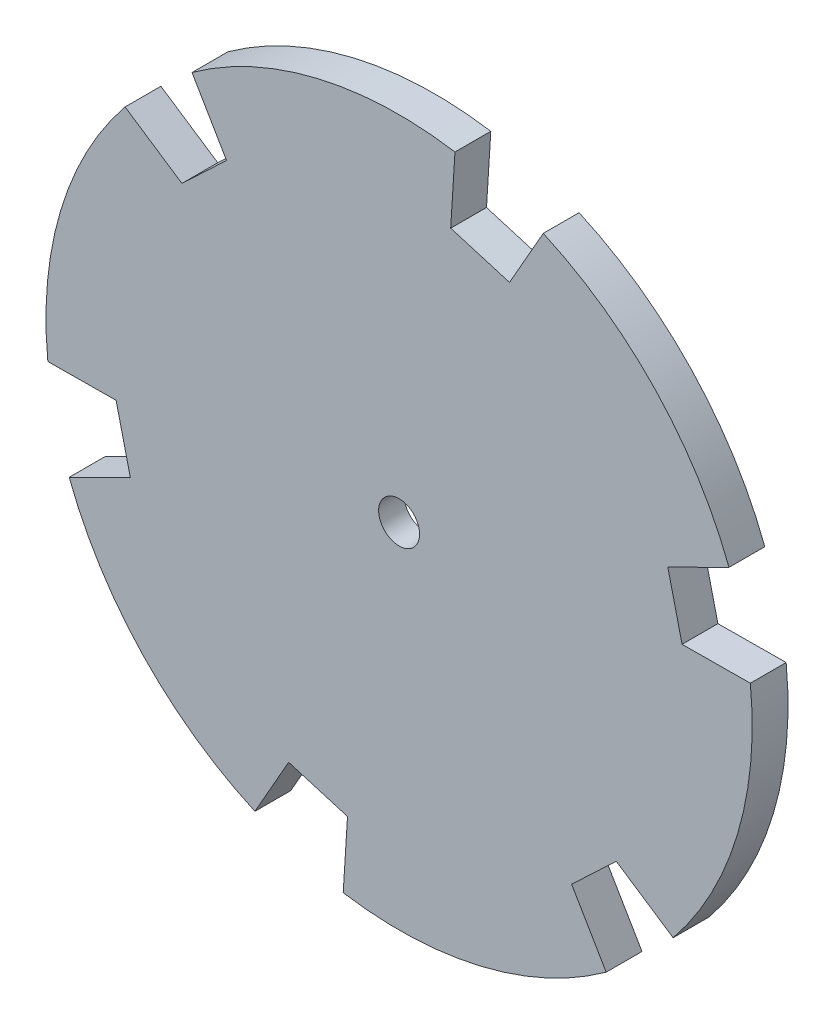
SolidWorks part; units mm, degrees
ref_plane "Front Plane" through (0, 0, 0) normal (0, 0, 1) x (1, 0, 0)
ref_plane "Top Plane" through (0, 0, 0) normal (0, 1, 0) x (1, 0, 0)
ref_plane "Right Plane" through (0, 0, 0) normal (1, 0, 0) x (0, 0, -1)
sketch "Sketch1" plane through (0, 0, 0) normal (0, 0, 1) x (1, 0, 0)
  line L18 (-20.2324, 27.9446) -> (-16.8562, 22.1912)
  line L19 (-16.8562, 22.1912) -> (-21.2157, 18.0687)
  line L20 (-21.2157, 18.0687) -> (-26.7716, 21.7608)
  line L21 (-34.3169, -3.5495) -> (-27.6463, -3.5023)
  line L22 (-27.6463, -3.5023) -> (-26.2558, -9.339)
  line L23 (-26.2558, -9.339) -> (-32.2312, -12.3045)
  line L24 (-14.0845, -31.4941) -> (-10.79, -25.6935)
  line L25 (-10.79, -25.6935) -> (-5.0401, -27.4076)
  line L26 (-5.0401, -27.4076) -> (-5.4596, -34.0653)
  line L27 (20.2324, -27.9446) -> (16.8562, -22.1912)
  line L28 (16.8562, -22.1912) -> (21.2157, -18.0687)
  line L29 (21.2157, -18.0687) -> (26.7716, -21.7608)
  line L30 (34.3169, 3.5495) -> (27.6463, 3.5023)
  line L31 (27.6463, 3.5023) -> (26.2558, 9.339)
  line L32 (26.2558, 9.339) -> (32.2312, 12.3045)
  line L33 (14.0845, 31.4941) -> (10.79, 25.6935)
  line L34 (10.79, 25.6935) -> (5.0401, 27.4076)
  line L35 (5.0401, 27.4076) -> (5.4596, 34.0653)
  line L36 (-20.2324, 27.9446) -> (-16.8562, 22.1912)
  line L37 (-16.8562, 22.1912) -> (-21.2157, 18.0687)
  line L38 (-21.2157, 18.0687) -> (-26.7716, 21.7608)
  line L39 (-34.3169, -3.5495) -> (-27.6463, -3.5023)
  line L40 (-27.6463, -3.5023) -> (-26.2558, -9.339)
  line L41 (-26.2558, -9.339) -> (-32.2312, -12.3045)
  line L42 (-14.0845, -31.4941) -> (-10.79, -25.6935)
  line L43 (-10.79, -25.6935) -> (-5.0401, -27.4076)
  line L44 (-5.0401, -27.4076) -> (-5.4596, -34.0653)
  line L45 (20.2324, -27.9446) -> (16.8562, -22.1912)
  line L46 (16.8562, -22.1912) -> (21.2157, -18.0687)
  line L47 (21.2157, -18.0687) -> (26.7716, -21.7608)
  line L48 (34.3169, 3.5495) -> (27.6463, 3.5023)
  line L49 (27.6463, 3.5023) -> (26.2558, 9.339)
  line L50 (26.2558, 9.339) -> (32.2312, 12.3045)
  line L51 (14.0845, 31.4941) -> (10.79, 25.6935)
  line L52 (10.79, 25.6935) -> (5.0401, 27.4076)
  line L53 (5.0401, 27.4076) -> (5.4596, 34.0653)
  arc A6 (-26.7716, 21.7608) -> (-34.3169, -3.5495) centre (0, 0) ccw
  arc A7 (-32.2312, -12.3045) -> (-14.0845, -31.4941) centre (0, 0) ccw
  arc A8 (-5.4596, -34.0653) -> (20.2324, -27.9446) centre (0, 0) ccw
  arc A9 (26.7716, -21.7608) -> (34.3169, 3.5495) centre (0, 0) ccw
  arc A10 (32.2312, 12.3045) -> (14.0845, 31.4941) centre (0, 0) ccw
  arc A11 (5.4596, 34.0653) -> (-20.2324, 27.9446) centre (0, 0) ccw
  arc A12 (-26.7716, 21.7608) -> (-34.3169, -3.5495) centre (0, 0) ccw
  arc A13 (-32.2312, -12.3045) -> (-14.0845, -31.4941) centre (0, 0) ccw
  arc A14 (-5.4596, -34.0653) -> (20.2324, -27.9446) centre (0, 0) ccw
  arc A15 (26.7716, -21.7608) -> (34.3169, 3.5495) centre (0, 0) ccw
  arc A16 (32.2312, 12.3045) -> (14.0845, 31.4941) centre (0, 0) ccw
  arc A17 (5.4596, 34.0653) -> (-20.2324, 27.9446) centre (0, 0) ccw
  dimension "D1" = 0
extrude "Boss-Extrude1" add sketch "Sketch1" along normal blind 2.5
sketch "Sketch2" plane through (0, 0, 0) normal (0, 0, -1) x (-1, 0, 0)
  line L18 (-5.4596, 34.0653) -> (-5.0401, 27.4076)
  line L19 (-5.0401, 27.4076) -> (-10.79, 25.6935)
  line L20 (-10.79, 25.6935) -> (-14.0845, 31.4941)
  line L21 (-32.2312, 12.3045) -> (-26.2558, 9.339)
  line L22 (-26.2558, 9.339) -> (-27.6463, 3.5023)
  line L23 (-27.6463, 3.5023) -> (-34.3169, 3.5495)
  line L24 (-26.7716, -21.7608) -> (-21.2157, -18.0687)
  line L25 (-21.2157, -18.0687) -> (-16.8562, -22.1912)
  line L26 (-16.8562, -22.1912) -> (-20.2324, -27.9446)
  line L27 (5.4596, -34.0653) -> (5.0401, -27.4076)
  line L28 (5.0401, -27.4076) -> (10.79, -25.6935)
  line L29 (10.79, -25.6935) -> (14.0845, -31.4941)
  line L30 (32.2312, -12.3045) -> (26.2558, -9.339)
  line L31 (26.2558, -9.339) -> (27.6463, -3.5023)
  line L32 (27.6463, -3.5023) -> (34.3169, -3.5495)
  line L33 (26.7716, 21.7608) -> (21.2157, 18.0687)
  line L34 (21.2157, 18.0687) -> (16.8562, 22.1912)
  line L35 (16.8562, 22.1912) -> (20.2324, 27.9446)
  line L36 (-5.4596, 34.0653) -> (-5.0401, 27.4076)
  line L37 (-5.0401, 27.4076) -> (-10.79, 25.6935)
  line L38 (-10.79, 25.6935) -> (-14.0845, 31.4941)
  line L39 (-32.2312, 12.3045) -> (-26.2558, 9.339)
  line L40 (-26.2558, 9.339) -> (-27.6463, 3.5023)
  line L41 (-27.6463, 3.5023) -> (-34.3169, 3.5495)
  line L42 (-26.7716, -21.7608) -> (-21.2157, -18.0687)
  line L43 (-21.2157, -18.0687) -> (-16.8562, -22.1912)
  line L44 (-16.8562, -22.1912) -> (-20.2324, -27.9446)
  line L45 (5.4596, -34.0653) -> (5.0401, -27.4076)
  line L46 (5.0401, -27.4076) -> (10.79, -25.6935)
  line L47 (10.79, -25.6935) -> (14.0845, -31.4941)
  line L48 (32.2312, -12.3045) -> (26.2558, -9.339)
  line L49 (26.2558, -9.339) -> (27.6463, -3.5023)
  line L50 (27.6463, -3.5023) -> (34.3169, -3.5495)
  line L51 (26.7716, 21.7608) -> (21.2157, 18.0687)
  line L52 (21.2157, 18.0687) -> (16.8562, 22.1912)
  line L53 (16.8562, 22.1912) -> (20.2324, 27.9446)
  circle A0 centre (0, 0) radius 3.875 construction
  circle A1 centre (0, 0) radius 3.875 construction
  circle A2 centre (0, 0) radius 4.075
  arc A6 (20.2324, 27.9446) -> (-5.4596, 34.0653) centre (0, 0) ccw
  arc A7 (-14.0845, 31.4941) -> (-32.2312, 12.3045) centre (0, 0) ccw
  arc A8 (-34.3169, 3.5495) -> (-26.7716, -21.7608) centre (0, 0) ccw
  arc A9 (-20.2324, -27.9446) -> (5.4596, -34.0653) centre (0, 0) ccw
  arc A10 (14.0845, -31.4941) -> (32.2312, -12.3045) centre (0, 0) ccw
  arc A11 (34.3169, -3.5495) -> (26.7716, 21.7608) centre (0, 0) ccw
  arc A12 (20.2324, 27.9446) -> (-5.4596, 34.0653) centre (0, 0) ccw
  arc A13 (-14.0845, 31.4941) -> (-32.2312, 12.3045) centre (0, 0) ccw
  arc A14 (-34.3169, 3.5495) -> (-26.7716, -21.7608) centre (0, 0) ccw
  arc A15 (-20.2324, -27.9446) -> (5.4596, -34.0653) centre (0, 0) ccw
  arc A16 (14.0845, -31.4941) -> (32.2312, -12.3045) centre (0, 0) ccw
  arc A17 (34.3169, -3.5495) -> (26.7716, 21.7608) centre (0, 0) ccw
  dimension "D1" = 0
  dimension "D2" = 0.2
extrude "Boss-Extrude2" add sketch "Sketch2" along normal up to surface (1 mm away)
sketch "Sketch3" plane through (0, 0, 0) normal (0, 0, -1) x (-1, 0, 0)
  circle A0 centre (0, 0) radius 2 construction
  circle A1 centre (0, 0) radius 2
extrude "Cut-Extrude1" cut sketch "Sketch3" against normal through all
